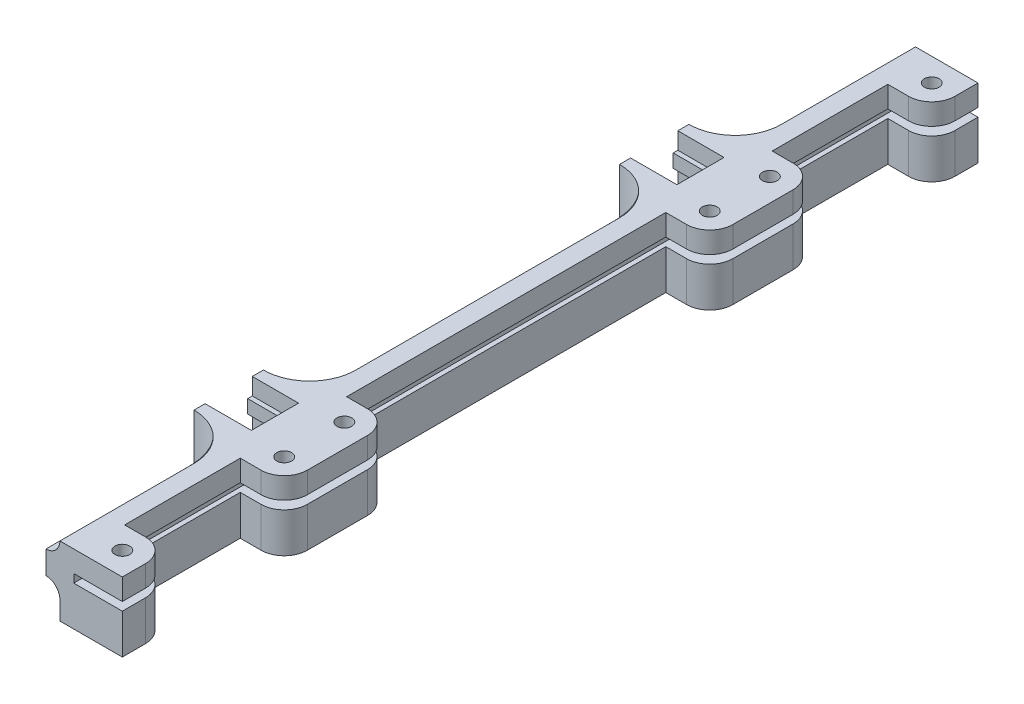
SolidWorks part; units mm, degrees
ref_plane "Front Plane" through (0, 0, 0) normal (0, 0, 1) x (1, 0, 0)
ref_plane "Top Plane" through (0, 0, 0) normal (0, 1, 0) x (1, 0, 0)
ref_plane "Right Plane" through (0, 0, 0) normal (1, 0, 0) x (0, 0, -1)
sketch "Esquisse2" plane through (0, 0, 0) normal (0, 0, 1) x (1, 0, 0)
  line L0 (10.5, 0.9) -> (0, 0.9)
  line L1 (0, 0.9) -> (0, -0.9)
  line L2 (0, -0.9) -> (10.5, -0.9)
  line L3 (10.5, -0.9) -> (10.5, -9.5)
  line L4 (10.5, -9.5) -> (-3, -9.5)
  line L5 (-3, 5.5) -> (-3, 2.5)
  line L6 (-3, 5.5) -> (10.5, 5.5)
  line L7 (10.5, 5.5) -> (10.5, 0.9)
  line L8 (-3, 2.5) -> (-6, 2.5)
  line L9 (-6, 2.5) -> (-6, -2.5)
  line L10 (-6, -2.5) -> (-3, -2.5)
  line L11 (-3, -2.5) -> (-3, -9.5)
  point P9 (0, 0)
  point P11 (-6, 0)
  dimension "D1" = 1.8
  dimension "D2" = 10.5
  dimension "D3" = 15
  dimension "D4" = 3
  dimension "D5" = 5
  dimension "D6" = 3
  dimension "D7" = 4.6
  dimension "D8" = 8.6
extrude "Main" add sketch "Esquisse2" along normal blind 185
sketch "Esquisse3" plane through (0, 5.5, 0) normal (0, 1, 0) x (1, 0, 0)
  line L0 (10.5, -185) -> (10.5, 0) construction
  line L1 (10.5, 0) -> (-3, 0) construction
  line L2 (10.5, -185) -> (-3, -185) construction
  circle A0 centre (5.5, -5) radius 1.6
  circle A1 centre (5.5, -40) radius 1.6
  circle A2 centre (5.5, -53) radius 1.6
  circle A5 centre (5.5, -145) radius 1.6
  circle A6 centre (5.5, -180) radius 1.6
  circle A7 centre (5.5, -132) radius 1.6
  dimension "D1" = 3.2
  dimension "D2" = 5
  dimension "D3" = 5
  dimension "D4" = 35
  dimension "D5" = 79
  dimension "D6" = 53
  dimension "D7" = 5
  dimension "D8" = 35
extrude "Holes" cut sketch "Esquisse3" against normal through all
sketch "Esquisse4" plane through (-3, 0, 0) normal (-1, 0, 0) x (0, 0, 1)
  line L0 (41.4, 5.5) -> (41.4, 1.85)
  line L1 (41.4, 1.85) -> (42.4, 1.85)
  line L2 (42.4, 1.85) -> (42.4, -1.05)
  line L3 (42.4, -1.05) -> (41.4, -1.05)
  line L4 (41.4, -1.05) -> (41.4, -4.7)
  line L5 (41.4, -4.7) -> (45.05, -4.7)
  line L6 (45.05, -4.7) -> (45.05, -3.7)
  line L7 (45.05, -3.7) -> (47.95, -3.7)
  line L8 (47.95, -3.7) -> (47.95, -4.7)
  line L9 (47.95, -4.7) -> (51.6, -4.7)
  line L10 (51.6, -4.7) -> (51.6, -1.05)
  line L11 (51.6, -1.05) -> (50.6, -1.05)
  line L12 (50.6, -1.05) -> (50.6, 1.85)
  line L13 (50.6, 1.85) -> (51.6, 1.85)
  line L14 (51.6, 1.85) -> (51.6, 5.5)
  line L15 (41.4, 5.5) -> (39, 5.5)
  line L17 (51.6, 5.5) -> (54, 5.5)
  line L18 (39, 5.5) -> (39, -9.5)
  line L19 (39, -9.5) -> (54, -9.5)
  line L20 (54, 5.5) -> (54, -9.5)
  line L28 (0, 5.5) -> (0, 2.5) construction
  line L29 (185, 5.5) -> (0, 5.5) construction
  line L30 (185, -9.5) -> (0, -9.5) construction
  dimension "D1" = 15
  dimension "D2" = 10.2
  dimension "D3" = 2.9
  dimension "D4" = 10.2
  dimension "D5" = 1
  dimension "D7" = 39
extrude "Fixing" add sketch "Esquisse4" along normal blind 10
sketch "Esquisse6" plane through (-3, 0, 0) normal (-1, 0, 0) x (0, 0, 1)
  line L0 (41.4, 2.5) -> (51.6, 2.5)
  line L1 (51.6, 2.5) -> (51.6, 1.85)
  line L2 (51.6, 1.85) -> (50.6, 1.85)
  line L3 (50.6, 1.85) -> (50.6, -1.05)
  line L4 (50.6, -1.05) -> (51.6, -1.05)
  line L5 (51.6, -1.05) -> (51.6, -2.5)
  line L6 (51.6, -2.5) -> (41.4, -2.5)
  line L8 (41.4, -4.7) -> (41.4, -1.05) construction
  line L11 (41.4, -2.5) -> (41.4, -1.05)
  line L12 (41.4, -1.05) -> (42.4, -1.05)
  line L13 (42.4, -1.05) -> (42.4, 1.85)
  line L14 (42.4, 1.85) -> (41.4, 1.85)
  line L15 (41.4, 1.85) -> (41.4, 2.5)
  line L16 (51.6, 2.5) -> (41.4, 2.5) construction
extrude "FixingHole" cut sketch "Esquisse6" along normal through all
fillet "Congé2" radius 10 2 edges at (-3, 4, 54) (-3, 4, 39)
sketch "Esquisse5" plane through (0, 5.5, 0) normal (0, 1, 0) x (1, 0, 0)
  line L0 (10.5, -185) -> (10.5, 0) construction
  line L1 (10.5, -10) -> (1, -10)
  line L2 (10.5, -10) -> (10.5, -35)
  line L3 (10.5, -35) -> (1, -35)
  line L4 (1, -10) -> (1, -35)
  line L5 (10.5, 0) -> (-3, 0) construction
  line L6 (10.5, -185) -> (-3, -185) construction
  line L7 (10.5, -58) -> (1, -58)
  line L8 (10.5, -58) -> (10.5, -127)
  line L9 (10.5, -127) -> (1, -127)
  line L10 (1, -58) -> (1, -127)
  line L11 (10.5, -150) -> (1, -150)
  line L12 (10.5, -150) -> (10.5, -175)
  line L13 (10.5, -175) -> (1, -175)
  line L14 (1, -150) -> (1, -175)
  circle A0 centre (5.5, -40) radius 1.6 construction
  circle A1 centre (5.5, -145) radius 1.6 construction
  circle A2 centre (5.5, -53) radius 1.6 construction
  circle A3 centre (5.5, -132) radius 1.6 construction
  dimension "D1" = 1
  dimension "D2" = 10
  dimension "D3" = 5
  dimension "D4" = 10
  dimension "D5" = 5
  dimension "D6" = 5
  dimension "D7" = 5
extrude "Enlèv. mat.-Extru.3" cut sketch "Esquisse5" against normal through all
pattern_linear "Répétition linéaire2" count 2 spacing 92 along (0, 0, 1) of "Fixing", "Congé2", "FixingHole"
fillet "Congé4" radius 3 14 edges at (-3, 2.5, 14.5) (-3, -2.5, 170.5) (-3, -2.5, 92.5) (-3, -2.5, 14.5) (-3, 2.5, 170.5) (-3, 2.5, 92.5) (-3.7805, 2.5, 152.127) (-3.7805, 2.5, 124.873) (-3.7805, 2.5, 60.127) (-3.7805, -2.5, 152.127) (-3.7805, -2.5, 124.873) (-3.7805, -2.5, 60.127) (-3.7805, -2.5, 32.873) (-3.7805, 2.5, 32.873)
fillet "Congé5" radius 5 12 edges at (10.5, -5.2, 10) (10.5, 3.2, 10) (10.5, -5.2, 175) (10.5, 3.2, 175) (10.5, 3.2, 127) (10.5, -5.2, 127) (10.5, -5.2, 150) (10.5, 3.2, 150) (10.5, -5.2, 58) (10.5, 3.2, 58) (10.5, -5.2, 35) (10.5, 3.2, 35)
